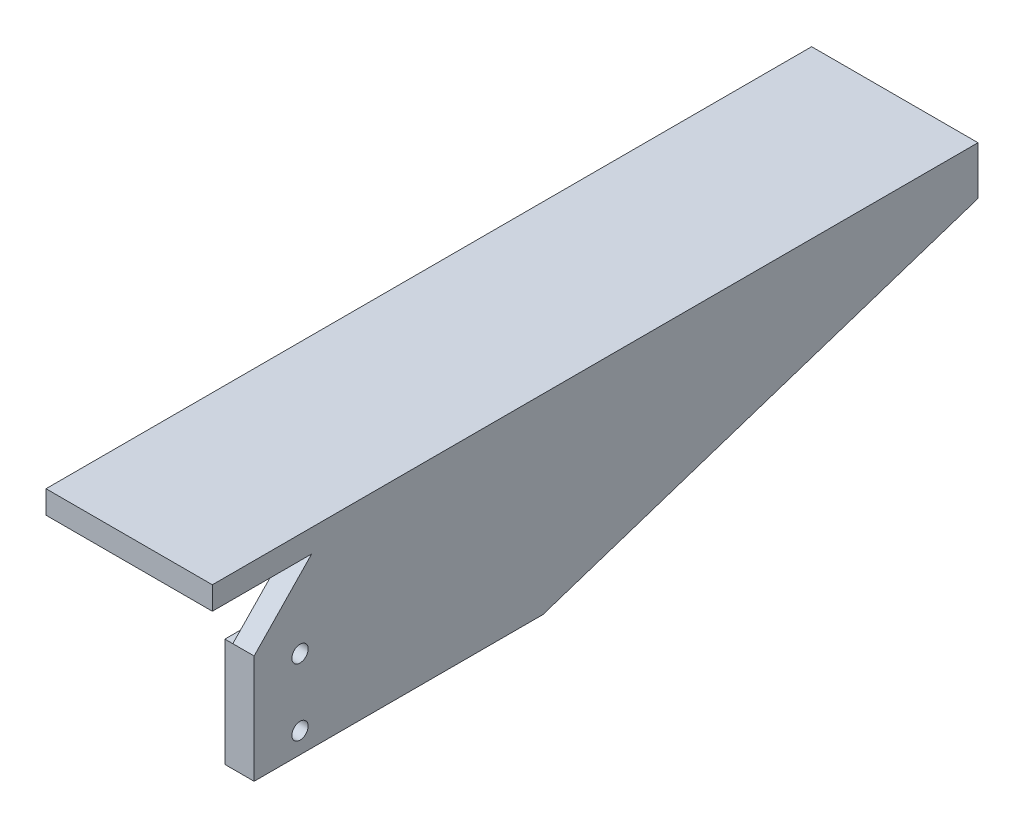
SolidWorks part; units mm, degrees
ref_plane "Front Plane" through (0, 0, 0) normal (0, 0, 1) x (1, 0, 0)
ref_plane "Top Plane" through (0, 0, 0) normal (0, 1, 0) x (1, 0, 0)
ref_plane "Right Plane" through (0, 0, 0) normal (1, 0, 0) x (0, 0, -1)
ref_plane "PY -20.700" through (0, -20.7, 0) normal (0, 1, 0) x (1, 0, 0)
sketch "leg and pad sketch" plane through (0, -20.7, 0) normal (0, 1, 0) x (1, 0, 0)
  line L0 (-0.5513, 30.3327) -> (-0.3673, 30.8194)
  line L1 (-0.3673, 30.8194) -> (-0.028, 31.2139)
  line L2 (-0.028, 31.2139) -> (0.4256, 31.4688)
  line L3 (0.4256, 31.4688) -> (0.939, 31.5534)
  line L4 (0.939, 31.5534) -> (1.4504, 31.4576)
  line L5 (1.4504, 31.4576) -> (1.8983, 31.1928)
  line L6 (1.8983, 31.1928) -> (2.2288, 30.7909)
  line L7 (2.2288, 30.7909) -> (2.4021, 30.3003)
  line L8 (2.4021, 30.3003) -> (2.3973, 29.78)
  line L9 (2.3973, 29.78) -> (2.2152, 29.2926)
  line L10 (2.2152, 29.2926) -> (1.8775, 28.8968)
  line L11 (1.8775, 28.8968) -> (1.4248, 28.6402)
  line L12 (1.4248, 28.6402) -> (0.9118, 28.5536)
  line L13 (0.9118, 28.5536) -> (0.4, 28.6475)
  line L14 (0.4, 28.6475) -> (0.4, -9.98)
  line L15 (0.4, -9.98) -> (1.92, -11.5)
  line L16 (1.92, -11.5) -> (1.92, -31.37)
  line L17 (1.92, -31.37) -> (8.92, -31.37)
  line L18 (8.92, -31.37) -> (8.92, 32.7926)
  line L19 (8.92, 32.7926) -> (-27.2048, 54.5947)
  line L20 (-27.2048, 54.5947) -> (-30.8218, 48.6015)
  line L21 (-30.8218, 48.6015) -> (-0.5513, 30.3327)
extrude "leg and pad" add sketch "leg and pad sketch" along normal mid plane 26
ref_plane "PX 1.350" through (1.35, 0, 0) normal (1, 0, 0) x (0, 0, -1)
sketch "screw head relief sketch" plane through (1.35, 0, 0) normal (1, 0, 0) x (0, 0, -1)
  line L0 (23.4, -12.7) -> (23.4, -6.7)
  line L1 (23.4, -6.7) -> (9.4, -6.7)
  line L2 (9.4, -6.7) -> (9.4, -12.7)
  line L3 (9.4, -12.7) -> (23.4, -12.7)
extrude "screw head relief" cut sketch "screw head relief sketch" against normal mid plane 4.7
sketch "insert flange relief sketch" plane through (0, -20.7, 0) normal (0, 1, 0) x (1, 0, 0)
  line L0 (-18.3249, 39.8914) -> (-17.0331, 42.0318)
  line L1 (-17.0331, 42.0318) -> (-9.7557, 37.6398)
  line L2 (-9.7557, 37.6398) -> (-11.0475, 35.4994)
  line L3 (-11.0475, 35.4994) -> (-18.3249, 39.8914)
revolve "insert flange relief" cut sketch "insert flange relief sketch" angle 360 about L0
sketch "M6 slot end 1 sketch" plane through (0, -20.7, 0) normal (0, 1, 0) x (1, 0, 0)
  line L0 (-20.8933, 41.4415) -> (-16.243, 49.147)
  line L1 (-16.243, 49.147) -> (-13.2464, 47.3385)
  line L2 (-13.2464, 47.3385) -> (-17.8968, 39.633)
  line L3 (-17.8968, 39.633) -> (-20.8933, 41.4415)
revolve "M6 slot end 1" cut sketch "M6 slot end 1 sketch" angle 360 about L0
sketch "M6 slot end 2 sketch" plane through (0, -20.7, 0) normal (0, 1, 0) x (1, 0, 0)
  line L0 (-15.7564, 38.3413) -> (-11.106, 46.0467)
  line L1 (-11.106, 46.0467) -> (-8.1094, 44.2382)
  line L2 (-8.1094, 44.2382) -> (-12.7598, 36.5328)
  line L3 (-12.7598, 36.5328) -> (-15.7564, 38.3413)
revolve "M6 slot end 2" cut sketch "M6 slot end 2 sketch" angle 360 about L0
sketch "M6 slot middle sketch" plane through (0, -20.7, 0) normal (0, 1, 0) x (1, 0, 0)
  line L0 (-15.7564, 38.3413) -> (-20.8933, 41.4415)
  line L1 (-20.8933, 41.4415) -> (-16.243, 49.147)
  line L2 (-16.243, 49.147) -> (-11.106, 46.0467)
  line L3 (-11.106, 46.0467) -> (-15.7564, 38.3413)
extrude "M6 slot middle" cut sketch "M6 slot middle sketch" against normal mid plane 7
ref_plane "PX 5.420" through (5.42, 0, 0) normal (1, 0, 0) x (0, 0, -1)
sketch "screw holes sketch" plane through (5.42, 0, 0) normal (1, 0, 0) x (0, 0, -1)
  circle A0 centre (-20.375, -28.7) radius 1.95
  circle A1 centre (-20.375, -12.7) radius 1.95
extrude "screw holes" cut sketch "screw holes sketch" against normal mid plane 9
ref_plane "PY -2.100" through (0, -2.1, 0) normal (0, 1, 0) x (1, 0, 0)
sketch "foot leg sketch" plane through (0, -2.1, 0) normal (0, 1, 0) x (1, 0, 0)
  line L0 (2.3, 30.0135) -> (2.3, -9.98)
  line L1 (2.3, -9.98) -> (8.92, -9.98)
  line L2 (8.92, -9.98) -> (8.92, 32.7926)
  line L3 (8.92, 32.7926) -> (-27.2048, 54.5947)
  line L4 (-27.2048, 54.5947) -> (-30.2017, 49.6289)
  line L5 (-30.2017, 49.6289) -> (2.3, 30.0135)
extrude "foot leg" add sketch "foot leg sketch" along normal mid plane 12.2
ref_plane "PY 7.785" through (0, 7.785, 0) normal (0, 1, 0) x (1, 0, 0)
sketch "sole under the housing sketch" plane through (0, 7.785, 0) normal (0, 1, 0) x (1, 0, 0)
  line L0 (-30.9218, 142) -> (8.92, 142)
  line L1 (8.92, 142) -> (8.92, -13.03)
  line L2 (8.92, -13.03) -> (-30.9218, -13.03)
  line L3 (-30.9218, -13.03) -> (-30.9218, 142)
extrude "sole under the housing" add sketch "sole under the housing sketch" along normal mid plane 8.57
ref_plane "PY 9.320" through (0, 9.32, 0) normal (0, 1, 0) x (1, 0, 0)
sketch "sole under the block sketch" plane through (0, 9.32, 0) normal (0, 1, 0) x (1, 0, 0)
  line L0 (-30.9218, -12.53) -> (8.92, -12.53)
  line L1 (8.92, -12.53) -> (8.92, -41.37)
  line L2 (8.92, -41.37) -> (-30.9218, -41.37)
  line L3 (-30.9218, -41.37) -> (-30.9218, -12.53)
extrude "sole under the block" add sketch "sole under the block sketch" along normal mid plane 5.5
ref_plane "PX 6.370" through (6.37, 0, 0) normal (1, 0, 0) x (0, 0, -1)
sketch "seat gusset sketch" plane through (6.37, 0, 0) normal (1, 0, 0) x (0, 0, -1)
  line L0 (-9.48, -8.2) -> (-31.37, -8.2)
  line L1 (-31.37, -8.2) -> (-31.37, -7.7)
  line L2 (-31.37, -7.7) -> (-17.1, 7.07)
  line L3 (-17.1, 7.07) -> (-9.48, 7.07)
  line L4 (-9.48, 7.07) -> (-9.48, -8.2)
extrude "seat gusset" add sketch "seat gusset sketch" along normal mid plane 5.1
ref_plane "PX -19.922" through (-19.9218, 0, 0) normal (1, 0, 0) x (0, 0, -1)
sketch "tail rib sketch" plane through (-19.9218, 0, 0) normal (1, 0, 0) x (0, 0, -1)
  line L0 (53.1, 4) -> (53.1, -12.5)
  line L1 (53.1, -12.5) -> (57.1, -12.5)
  line L2 (57.1, -12.5) -> (140, 3.5)
  line L3 (140, 3.5) -> (140, 4)
  line L4 (140, 4) -> (53.1, 4)
extrude "tail rib" add sketch "tail rib sketch" along normal mid plane 6
ref_plane "PX 5.210" through (5.21, 0, 0) normal (1, 0, 0) x (0, 0, -1)
sketch "side brace sketch" plane through (5.21, 0, 0) normal (1, 0, 0) x (0, 0, -1)
  line L0 (142, 4) -> (142, 0.5)
  line L1 (142, 0.5) -> (37.7926, -33.7)
  line L2 (37.7926, -33.7) -> (31.7926, -33.7)
  line L3 (31.7926, -33.7) -> (31.7926, 4)
  line L4 (31.7926, 4) -> (142, 4)
extrude "side brace" add sketch "side brace sketch" along normal mid plane 7.42
sketch "screw head relief to the end sketch" plane through (1.35, 0, 0) normal (1, 0, 0) x (0, 0, -1)
  line L0 (23.4, -12.7) -> (23.4, 3.3)
  line L1 (23.4, 3.3) -> (9.4, 3.3)
  line L2 (9.4, 3.3) -> (9.4, -12.7)
  line L3 (9.4, -12.7) -> (23.4, -12.7)
extrude "screw head relief to the end" cut sketch "screw head relief to the end sketch" against normal mid plane 4.7
equation "\"diffL\" = 608.8mm"
equation "\"diffW\" = 329.4mm"
equation "\"diffT\" = 2.9mm"
equation "\"chanSlotW\" = 12.9mm"
equation "\"chanSlotDepth\" = 11.13mm"
equation "\"chanFloor\" = 1.57mm"
equation "\"chanLeg\" = 12.7mm"
equation "\"lightL\" = 604.8mm"
equation "\"lightW\" = 330.2mm"
equation "\"lightH\" = 92mm"
equation "\"lightSideFlat\" = 30mm"
equation "\"lightSlopeLen\" = 38.9mm"
equation "\"lightWingDepth\" = 50.1mm"
equation "\"lightWingFlat\" = 90.2mm"
equation "\"lightChanW\" = 99.6mm"
equation "\"lightChanStand\" = 44.1mm"
equation "\"insFlangeD\" = 12.3mm"
equation "\"insFromEnd\" = 20.7mm"
equation "\"insUpSlope\" = 20.8mm"
equation "\"gaugeH\" = 10mm"
equation "\"gaugeStepLen\" = 14mm"
equation "\"gaugeStepW0\" = 13.1mm"
equation "\"gaugeStepDW\" = 0.2mm"
equation "\"gaugeSteps\" = 5mm"
equation "\"gaugeHandleLen\" = 30mm"
equation "\"gaugeHandleW\" = 24mm"
equation "\"gaugeSlot0\" = 3mm"
equation "\"gaugeSlotD\" = 0.1mm"
equation "\"gaugeSlotDepth\" = 8mm"
equation "\"gap\" = 25.4mm"
equation "\"edgeL\" = 1mm"
equation "\"edgeW\" = 0.75mm"
equation "\"proud\" = 1.5mm"
equation "\"seatClr\" = 0.15mm"
equation "\"tongueClrZ\" = 0.1mm"
equation "\"tongueClrX\" = 0.25mm"
equation "\"tongueLen\" = 30mm"
equation "\"armSide\" = 45mm"
equation "\"armEnd\" = 20mm"
equation "\"cornerCham\" = 3mm"
equation "\"brkW\" = 26mm"
equation "\"brkT\" = 7mm"
equation "\"brkSeatClr\" = 0.3mm"
equation "\"brkScrewSpan\" = 16mm"
equation "\"pilotD\" = 2.7mm"
equation "\"pilotDepth\" = 10mm"
equation "\"screwClrD\" = 3.9mm"
equation "\"jogBelow\" = 4mm"
equation "\"padT\" = 7mm"
equation "\"padLen\" = 36mm"
equation "\"m6Clr\" = 7mm"
equation "\"m6Slot\" = 6mm"
equation "\"flangeRelD\" = 17mm"
equation "\"flangeRelDepth\" = 1.5mm"
equation "\"relLen\" = 5mm"
equation "\"relDepth\" = 3.3mm"
equation "\"knockN\" = 100mm"
equation "\"petgcfE\" = 3000mm"
equation "\"mockExtent\" = 110mm"
equation "\"relZnear\" = 9.4mm"
equation "\"relZfar\" = 23.4mm"
equation "\"headD\" = 8mm"
equation "\"headH\" = 2.5mm"
equation "\"headFromEnd\" = 6.8mm"
equation "\"headBack\" = 16.4mm"
equation "\"sideClr\" = 0.4mm"
equation "\"cornerRelR\" = 1.5mm"
equation "\"cornerRelBack\" = 0.6mm"
equation "\"endHeadH\" = 2.8mm"
equation "\"footClr\" = 1.2mm"
equation "\"footEndClr\" = 3.5mm"
equation "\"footLift\" = 3.5mm"
equation "\"footBlockClr\" = 0.5mm"
equation "\"footBack\" = 30mm"
equation "\"footFwd\" = 25mm"
equation "\"footRibH\" = 16mm"
equation "\"footRibT\" = 6mm"
equation "\"footBraceEnd\" = 3mm"
equation "\"footLoadN\" = 25mm"
